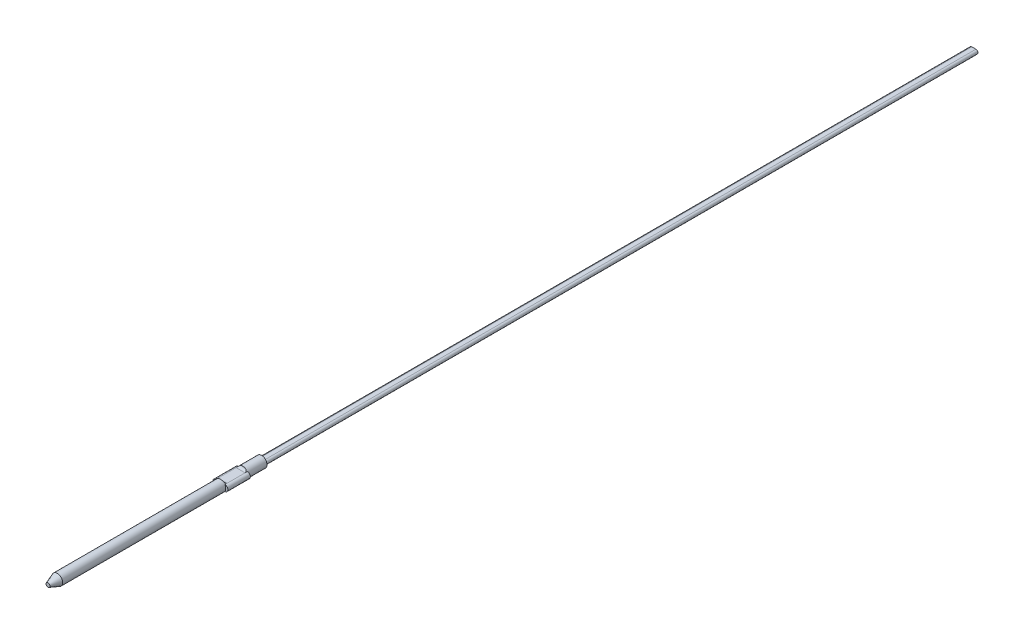
SolidWorks part; units mm, degrees
ref_plane "Front Plane" through (0, 0, 0) normal (0, 0, 1) x (1, 0, 0)
ref_plane "Top Plane" through (0, 0, 0) normal (0, 1, 0) x (1, 0, 0)
ref_plane "Right Plane" through (0, 0, 0) normal (1, 0, 0) x (0, 0, -1)
sketch "Sketch1" plane through (0, 0, 0) normal (0, 0, 1) x (1, 0, 0)
  circle A0 centre (0, 0) radius 1.8161
  dimension "D1" = 3.6322
extrude "Boss-Extrude1" add sketch "Sketch1" along normal blind 38.1
chamfer "Chamfer1" distance 3.175 angle 20 1 edges at (1.8161, 0, 38.1) first distance on face at (1.8161, 0, 38.1)
ref_plane "silicone_edge" through (0, 0, 0) normal (0, 0, -1) x (-1, 0, 0)
ref_plane "sheetmetal" through (0, 0, -2.54) normal (0, 0, -1) x (-1, 0, 0)
sketch "Sketch2" plane through (0, 0, 0) normal (0, 0, -1) x (-1, 0, 0)
  circle A1 centre (0, 0) radius 1.8161
  circle A2 centre (0, 0) radius 1.8161
  dimension "D1" = 0
extrude "Boss-Extrude2" add sketch "Sketch2" along normal up to surface (2.54 mm away) up to plane "sheetmetal"
ref_plane "crimp" through (0, 0, -20.32) normal (0, 0, -1) x (-1, 0, 0)
sketch "Sketch3" plane through (0, 0, -2.54) normal (0, 0, -1) x (-1, 0, 0)
  circle A1 centre (0, 0) radius 1.8161
  circle A2 centre (0, 0) radius 1.8161
  dimension "D1" = 0
extrude "Boss-Extrude3" add sketch "Sketch3" along normal up to surface (17.78 mm away) up to plane "crimp"
sketch "Sketch4" plane through (0, 0, -20.32) normal (0, 0, -1) x (-1, 0, 0)
  line L0 (-1.524, 0) -> (1.524, 0) construction
  line L1 (-1.524, 1.016) -> (1.524, 1.016)
  line L2 (-1.524, -1.016) -> (1.524, -1.016)
  line L3 (0, 0) -> (3.4487, 0) construction
  line L4 (0, 0) -> (0, 2.268) construction
  arc A0 (-1.524, 1.016) -> (-1.524, -1.016) centre (-1.524, 0) ccw
  arc A1 (1.524, -1.016) -> (1.524, 1.016) centre (1.524, 0) ccw
  point P2 (0, 0)
  dimension "D1" = 2.032
  dimension "D2" = 3.048
extrude "Boss-Extrude4" add sketch "Sketch4" along normal blind 7.62
sketch "Sketch5" plane through (0, 0, -27.94) normal (0, 0, -1) x (-1, 0, 0)
  arc A0 (-1.5054, -1.0158) -> (1.5054, -1.0158) centre (0, 0) ccw construction
  arc A1 (1.5054, -1.0158) -> (-1.5054, -1.0158) centre (0, 0) ccw construction
  arc A2 (-1.5054, -1.0158) -> (1.5054, -1.0158) centre (0, 0) ccw
  arc A3 (1.5054, -1.0158) -> (-1.5054, -1.0158) centre (0, 0) ccw
extrude "Boss-Extrude5" add sketch "Sketch5" along normal blind 6.35
sketch "Sketch6" plane through (0, 0, -34.29) normal (0, 0, -1) x (-1, 0, 0)
  line L0 (0.6985, 0) -> (-0.6985, 0) construction
  line L1 (0.6985, -0.6985) -> (-0.6985, -0.6985)
  line L2 (0.6985, 0.6985) -> (-0.6985, 0.6985)
  line L3 (0.8907, 0) -> (-0.8553, 0) construction
  line L4 (0, 1.278) -> (0, -1.5933) construction
  arc A0 (0.6985, -0.6985) -> (0.6985, 0.6985) centre (0.6985, 0) ccw
  arc A1 (-0.6985, 0.6985) -> (-0.6985, -0.6985) centre (-0.6985, 0) ccw
  point P2 (0, 0)
  dimension "D1" = 1.397
  dimension "D2" = 1.397
extrude "Boss-Extrude6" add sketch "Sketch6" along normal blind 241.3
fillet "Fillet2" radius 0.762 4 edges at (0, 1.016, -27.94) (0, 1.016, -20.32) (0, -1.016, -27.94) (0, -1.016, -20.32)
